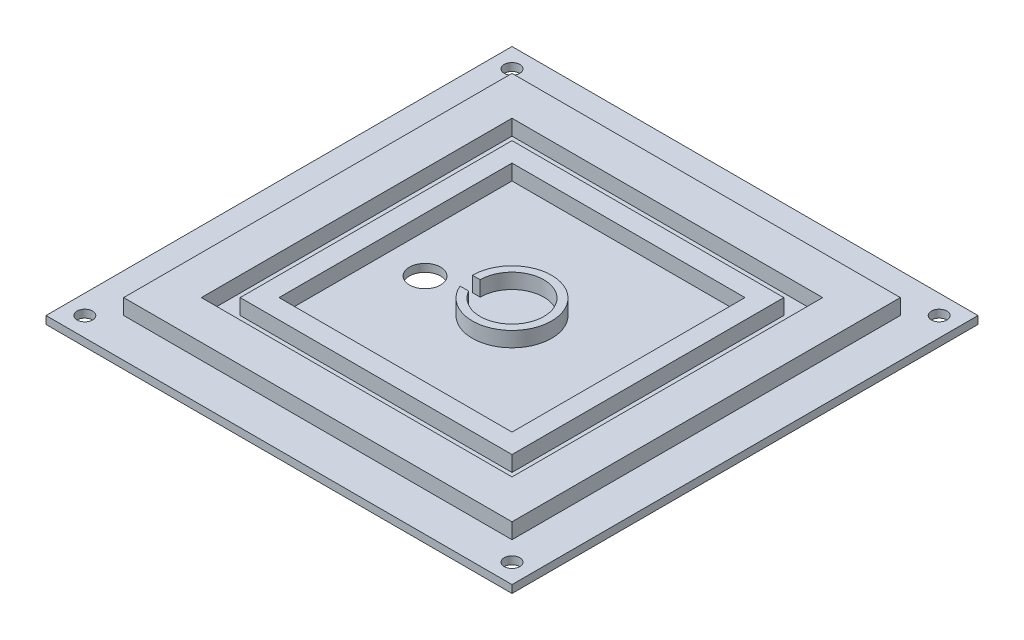
SolidWorks part; units mm, degrees
ref_plane "Front Plane" through (0, 0, 0) normal (0, 0, 1) x (1, 0, 0)
ref_plane "Top Plane" through (0, 0, 0) normal (0, 1, 0) x (1, 0, 0)
ref_plane "Right Plane" through (0, 0, 0) normal (1, 0, 0) x (0, 0, -1)
sketch "Sketch1" plane through (0, 0, 0) normal (0, 1, 0) x (1, 0, 0)
  line L1 (-76.2, 76.2) -> (76.2, 76.2)
  line L2 (-76.2, 76.2) -> (-76.2, -76.2)
  line L3 (-76.2, -76.2) -> (76.2, -76.2)
  line L4 (76.2, 76.2) -> (76.2, -76.2)
  line L5 (-76.2, 76.2) -> (76.2, -76.2) construction
  line L6 (-76.2, -76.2) -> (76.2, 76.2) construction
  point P0 (0, 0)
  dimension "D1" = 152.4
  dimension "D2" = 152.4
extrude "Boss-Extrude1" add sketch "Sketch1" against normal blind 2.54
sketch "Sketch2" plane through (0, 0, 0) normal (0, 1, 0) x (1, 0, 0)
  line L1 (63.5, -63.5) -> (-63.5, -63.5)
  line L2 (63.5, -63.5) -> (63.5, 63.5)
  line L3 (63.5, 63.5) -> (-63.5, 63.5)
  line L4 (-63.5, -63.5) -> (-63.5, 63.5)
  line L5 (63.5, -63.5) -> (-63.5, 63.5) construction
  line L6 (63.5, 63.5) -> (-63.5, -63.5) construction
  line L7 (-57.15, 57.15) -> (57.15, 57.15)
  line L8 (-57.15, 57.15) -> (-57.15, -57.15)
  line L9 (-57.15, -57.15) -> (57.15, -57.15)
  line L10 (57.15, 57.15) -> (57.15, -57.15)
  line L11 (-57.15, 57.15) -> (57.15, -57.15) construction
  line L12 (-57.15, -57.15) -> (57.15, 57.15) construction
  point P0 (0, 0)
  point P6 (0, 0)
  dimension "D1" = 127
  dimension "D2" = 127
  dimension "D3" = 114.3
  dimension "D4" = 114.3
extrude "Boss-Extrude3" add sketch "Sketch2" along normal blind 5.08 contours L2 L1 L4 L3
sketch "Sketch3" plane through (0, 5.08, 0) normal (0, 1, 0) x (1, 0, 0)
  line L1 (-50.8, 50.8) -> (50.8, 50.8)
  line L2 (-50.8, 50.8) -> (-50.8, -50.8)
  line L3 (-50.8, -50.8) -> (50.8, -50.8)
  line L4 (50.8, 50.8) -> (50.8, -50.8)
  line L5 (-50.8, 50.8) -> (50.8, -50.8) construction
  line L6 (-50.8, -50.8) -> (50.8, 50.8) construction
  point P0 (0, 0)
  dimension "D1" = 101.6
  dimension "D2" = 101.6
extrude "Cut-Extrude2" cut sketch "Sketch3" against normal blind 5.08
sketch "Sketch5" plane through (0, 0, 0) normal (0, 1, 0) x (1, 0, 0)
  line L1 (-44.45, 44.45) -> (44.45, 44.45)
  line L2 (-44.45, 44.45) -> (-44.45, -44.45)
  line L3 (-44.45, -44.45) -> (44.45, -44.45)
  line L4 (44.45, 44.45) -> (44.45, -44.45)
  line L5 (-44.45, 44.45) -> (44.45, -44.45) construction
  line L6 (-44.45, -44.45) -> (44.45, 44.45) construction
  point P0 (0, 0)
  dimension "D1" = 88.9
  dimension "D2" = 88.9
extrude "Boss-Extrude4" add sketch "Sketch5" along normal blind 5.08
sketch "Sketch6" plane through (0, 5.08, 0) normal (0, 1, 0) x (1, 0, 0)
  line L1 (-38.1, 38.1) -> (38.1, 38.1)
  line L2 (-38.1, 38.1) -> (-38.1, -38.1)
  line L3 (-38.1, -38.1) -> (38.1, -38.1)
  line L4 (38.1, 38.1) -> (38.1, -38.1)
  line L5 (-38.1, 38.1) -> (38.1, -38.1) construction
  line L6 (-38.1, -38.1) -> (38.1, 38.1) construction
  point P0 (0, 0)
  dimension "D1" = 76.2
  dimension "D2" = 76.2
extrude "Cut-Extrude3" cut sketch "Sketch6" against normal blind 5.08
sketch "Sketch7" plane through (0, 0, 0) normal (0, 1, 0) x (1, 0, 0)
  line L0 (-10.414, 0) -> (-12.954, 0)
  line L1 (-9.0909, -5.08) -> (-11.9164, -5.08)
  line L2 (-38.1, -38.1) -> (38.1, -38.1) construction
  arc A0 (-11.9164, -5.08) -> (-12.954, 0) centre (0, 0) ccw
  arc A1 (-9.0909, -5.08) -> (-10.414, 0) centre (0, 0) ccw
  dimension "D1" = 12.954
  dimension "D2" = 10.414
  dimension "D3" = 5.08
  dimension "D4" = 33.02
extrude "Boss-Extrude5" add sketch "Sketch7" along normal blind 2.794
sketch "Sketch8" plane through (0, 0, 0) normal (0, 1, 0) x (1, 0, 0)
  line L0 (-38.1, -38.1) -> (38.1, -38.1) construction
  circle A1 centre (-25.4, -3.048) radius 5.08
  dimension "D2" = 10.16
  dimension "D3" = 25.4
  dimension "D4" = 35.052
extrude "Cut-Extrude4" cut sketch "Sketch8" against normal through all contours A1
sketch "Sketch9" plane through (0, 0, 0) normal (0, 1, 0) x (1, 0, 0)
  line L0 (-76.2, -76.2) -> (76.2, -76.2) construction
  line L1 (-76.2, 76.2) -> (-76.2, -76.2) construction
  line L2 (76.2, -76.2) -> (76.2, 76.2) construction
  line L3 (76.2, 76.2) -> (-76.2, 76.2) construction
  circle A0 centre (-69.85, -69.85) radius 2.54
  circle A1 centre (69.85, -69.85) radius 2.54
  circle A2 centre (69.85, 69.85) radius 2.54
  circle A3 centre (-69.85, 69.85) radius 2.54
  dimension "D3" = 5.08
  dimension "D4" = 5.08
  dimension "D6" = 5.08
  dimension "D7" = 5.08
  dimension "D1" = 6.35
  dimension "D2" = 6.35
  dimension "D5" = 6.35
  dimension "D8" = 6.35
  dimension "D9" = 6.35
  dimension "D10" = 6.35
  dimension "D11" = 6.35
  dimension "D12" = 6.35
extrude "Cut-Extrude5" cut sketch "Sketch9" against normal through all
extrude "Boss-Extrude6" add sketch "Sketch7<2>" along normal blind 4.9276
sketch "Sketch7<2>" plane through (0, 0, 0) normal (0, 1, 0) x (1, 0, 0) same geometry as "Sketch7"
